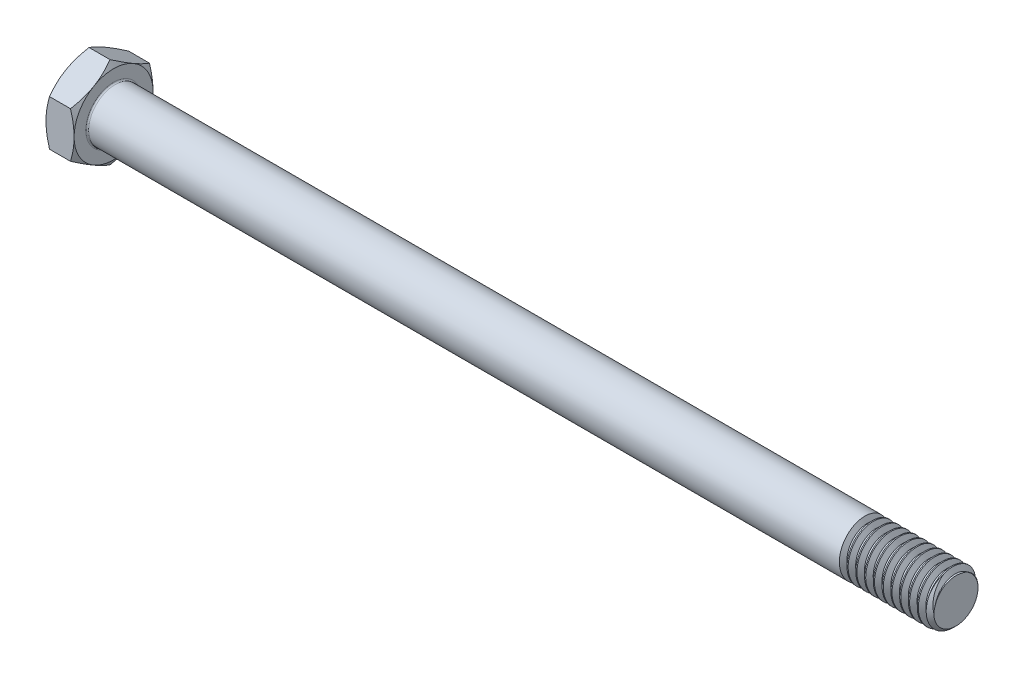
SolidWorks part; units mm, degrees
material "Plain Carbon Steel"
ref_plane "Front Plane" through (0, 0, 0) normal (0, 0, 1) x (1, 0, 0)
ref_plane "Top Plane" through (0, 0, 0) normal (0, 1, 0) x (1, 0, 0)
ref_plane "Right Plane" through (0, 0, 0) normal (1, 0, 0) x (0, 0, -1)
sketch "Sketch1" plane through (0, 0, 0) normal (0, 0, 1) x (1, 0, 0)
  line L0 (0, 0) -> (157.48, 0) construction
  line L1 (157.48, 0) -> (157.48, 4.0005)
  line L3 (156.718, 4.7625) -> (5.334, 4.7625)
  line L4 (5.08, 5.0165) -> (5.08, 7.1437)
  line L5 (5.08, 7.1437) -> (4.4419, 8.2489)
  line L6 (4.4419, 8.2489) -> (0.6381, 8.2489)
  line L7 (0.6381, 8.2489) -> (0, 7.1438)
  line L8 (0, 7.1438) -> (0, 0)
  line L9 (157.48, 4.0005) -> (156.718, 4.7625)
  line L10 (0, 8.2489) -> (-7.1438, 4.1244) construction
  line L11 (-7.1438, 4.1244) -> (-7.1438, -4.1244) construction
  line L12 (-7.1438, -4.1244) -> (0, -8.2489) construction
  line L13 (0, -8.2489) -> (7.1437, -4.1244) construction
  line L14 (7.1437, -4.1244) -> (7.1437, 4.1244) construction
  line L15 (7.1437, 4.1244) -> (0, 8.2489) construction
  line L16 (0, 0) -> (157.48, 0)
  arc A0 (5.334, 4.7625) -> (5.08, 5.0165) centre (5.334, 5.0165) cw
  circle A1 centre (0, 0) radius 7.1438 construction
  point P5 (157.48, 4.7625)
  dimension "D5" = 14.2875
  dimension "D7" = 0.254
  dimension "D1" = 9.525
  dimension "D2" = 152.4
  dimension "D3" = 30
  dimension "D6" = 5.08
revolve "Revolve1" add sketch "Sketch1" angle 360 about L16
sketch "Sketch2" plane through (0, 0, 0) normal (-1, 0, 0) x (0, 0, 1)
  line L1 (0, 8.2489) -> (-7.1438, 4.1244)
  line L2 (-7.1438, 4.1244) -> (-7.1437, -4.1244)
  line L3 (-7.1437, -4.1244) -> (0, -8.2489)
  line L4 (0, -8.2489) -> (7.1438, -4.1244)
  line L5 (7.1438, -4.1244) -> (7.1437, 4.1244)
  line L6 (7.1437, 4.1244) -> (0, 8.2489)
  circle A0 centre (0, 0) radius 7.1438 construction
  circle A1 centre (0, 0) radius 8.2489 construction
extrude "Cut-Extrude1" cut sketch "Sketch2" against normal through all flip side to cut
thread "Thread1" pitch 1.5875 method cut profile "Thread Profile1" start angle 0, offset 2.54, length 18.415, pitch 1.5875, diameter 9.525
ref_plane "Plane1" through (160.02, 0, 4.7625) normal (0, -1, 0) x (0, 0, 1)
sketch "Thread Profile1" plane through (160.02, 0, 4.7625) normal (0, -1, 0) x (0, 0, 1)
  line L0 (0, 0) -> (0, 1.5875) construction
  line L11 (0, 0) -> (0, 1.3891)
  line L12 (0, 1.3891) -> (-0.8593, 0.893)
  line L13 (-0.8593, 0.893) -> (-0.8593, 0.4961)
  line L15 (-0.8593, 0.4961) -> (0, 0)
  line L17 (-0.8593, 0.6945) -> (0, 0.6945) construction
  point P2 (0, 0)
  dimension "Pitch" = 1.5875
  dimension "Profile_Angle" = 60
  dimension "Profile_Land" = 0.3969
  dimension "Profile_Height" = 0.8593
sketch "Sketch6" plane through (0, -0.0007, 0.0005) normal (0, 0.809, -0.5878) x (1, 0, 0)
  line L4 (141.108, 3.9007) -> (141.6041, 4.76)
  line L5 (141.6041, 4.76) -> (140.215, 4.76)
  line L6 (140.215, 4.76) -> (140.7111, 3.9007)
  line L7 (140.7111, 3.9007) -> (141.108, 3.9007)
  line L8 (141.108, 3.9007) -> (141.6041, 4.76)
  line L9 (141.6041, 4.76) -> (140.215, 4.76)
  line L10 (140.215, 4.76) -> (140.7111, 3.9007)
  line L11 (140.7111, 3.9007) -> (141.108, 3.9007)
  dimension "D1" = 0
extrude "Cut-Extrude2" cut sketch "Sketch6" against normal through all
